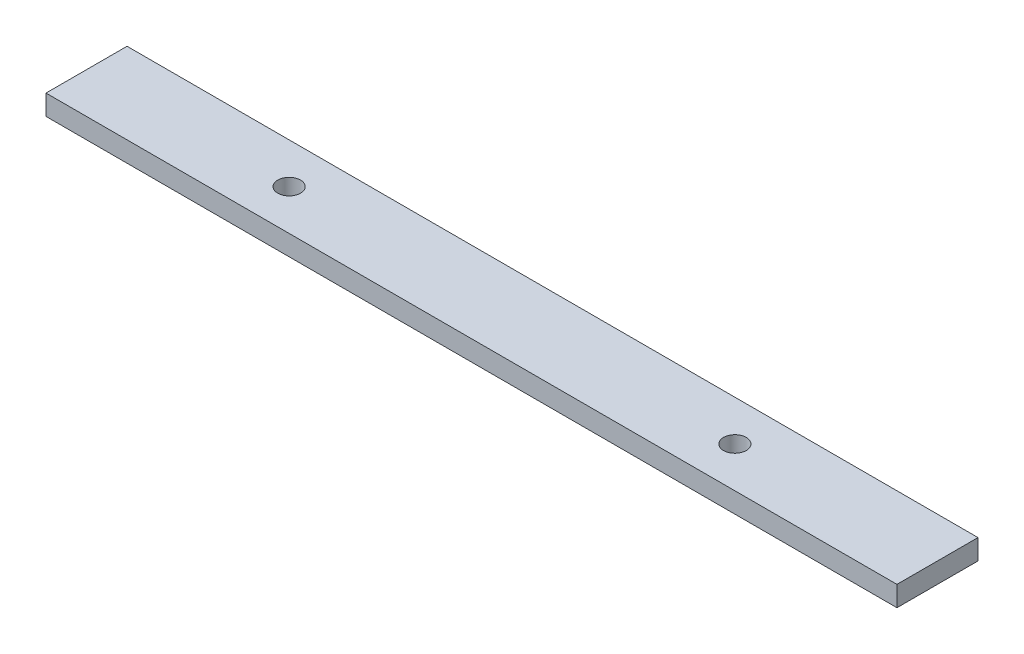
SolidWorks part; units mm, degrees
ref_plane "Front Plane" through (0, 0, 0) normal (0, 0, 1) x (1, 0, 0)
ref_plane "Top Plane" through (0, 0, 0) normal (0, 1, 0) x (1, 0, 0)
ref_plane "Right Plane" through (0, 0, 0) normal (1, 0, 0) x (0, 0, -1)
sketch "Sketch1" plane through (0, 0, 0) normal (0, 1, 0) x (1, 0, 0)
  line L1 (-133.35, 12.7) -> (133.35, 12.7)
  line L2 (-133.35, 12.7) -> (-133.35, -12.7)
  line L3 (-133.35, -12.7) -> (133.35, -12.7)
  line L4 (133.35, 12.7) -> (133.35, -12.7)
  line L5 (-133.35, 12.7) -> (133.35, -12.7) construction
  line L6 (-133.35, -12.7) -> (133.35, 12.7) construction
  point P0 (0, 0)
  dimension "D1" = 266.7
  dimension "D2" = 25.4
extrude "Boss-Extrude1" add sketch "Sketch1" along normal blind 6.35
hole_wizard "1/4 Clearance Hole2" positions "Sketch2" profile "Sketch3" hole size "1/4" standard "ANSI Inch" end condition through all
sketch "Sketch2" plane through (0, 6.35, 0) normal (0, 1, 0) x (1, 0, 0)
  line L1 (-69.85, 0) -> (69.85, 0)
  point P3 (-69.85, 0)
  point P4 (69.85, 0)
  point P8 (0, 0)
  dimension "D1" = 139.7
sketch "Sketch3" plane through (-69.85, 6.35, 0) normal (1, 0, 0) x (0, 0, 1)
  line L0 (0, 0) -> (0, 6.35)
  line L1 (0, 6.35) -> (3.5712, 6.35)
  line L2 (3.5712, 6.35) -> (3.5712, 0)
  line L5 (3.5712, 0) -> (0, 0)
  line L11 (0, -6.35) -> (0, 107.95) construction
  dimension "Thru Hole Dia." = 7.1425
  dimension "Thru Hole Depth" = 6.35
